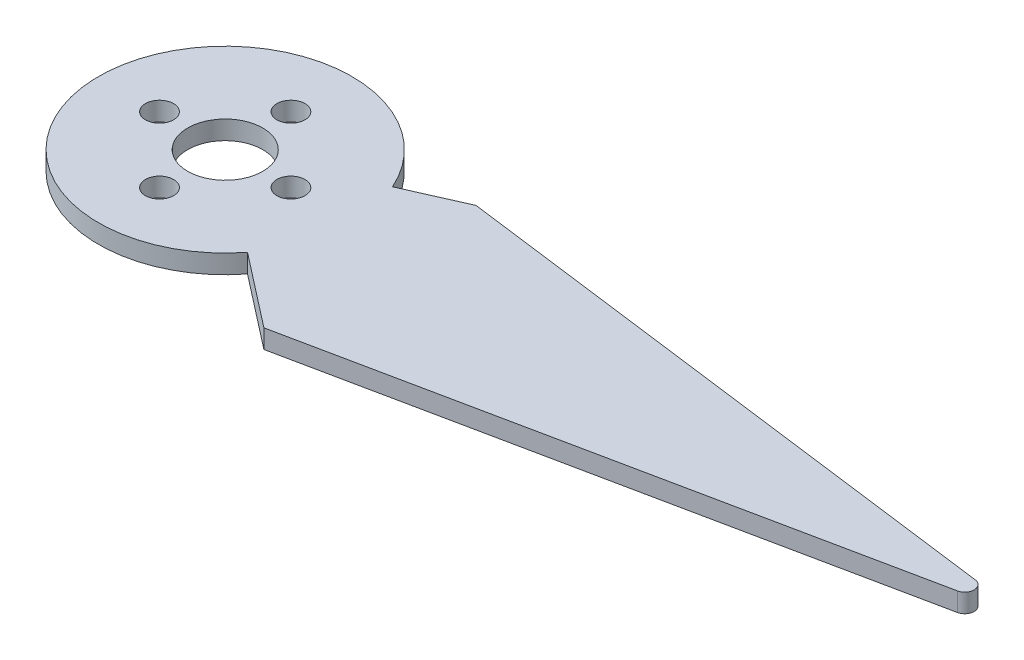
SolidWorks part; units mm, degrees
ref_plane "Alzado" through (0, 0, 0) normal (0, 0, 1) x (1, 0, 0)
ref_plane "Planta" through (0, 0, 0) normal (0, 1, 0) x (1, 0, 0)
ref_plane "Vista lateral" through (0, 0, 0) normal (1, 0, 0) x (0, 0, -1)
sketch "Croquis7" plane through (0, 0, 0) normal (0, 1, 0) x (1, 0, 0)
  line L0 (10.6592, -8.2848) -> (18.5, -14.3789)
  line L1 (18.5, -14.3789) -> (79.7101, -1.7047)
  line L2 (79.6363, 0.2662) -> (18.5, 8.2157)
  line L3 (18.5, 8.2157) -> (12.3377, 5.4806)
  line L4 (18.5, 8.2157) -> (18.5, -14.3789) construction
  arc A0 (10.6592, -8.2848) -> (12.3377, 5.4806) centre (0, 0) cw
  arc A1 (79.7101, -1.7047) -> (79.6363, 0.2662) centre (79.5074, -0.7255) ccw
  point P8 (85.5284, -0.5)
  dimension "D1" = 13.5002
  dimension "D2" = 1
  dimension "D4" = 12.3377
  dimension "D5" = 18.5
  dimension "D6" = 85.5284
  dimension "D7" = 8.2157
  dimension "D8" = 0.5
  dimension "D9" = 8.2848
base flange "Brida base1" sketch "Croquis7" thickness 2 reverse thickness direction no parameters "D1"=1
sketch "Croquis12" plane through (0, 0, 0) normal (0, 1, 0) x (1, 0, 0)
  circle A0 centre (0, 0) radius 4
  dimension "D1" = 8
extrude "Cortar-Extruir1" cut sketch "Croquis12" against normal blind 2 normal cut yes
sketch "Croquis13" plane through (0, 0, 0) normal (0, 1, 0) x (1, 0, 0)
  circle A0 centre (0, 7) radius 1.5
extrude "Cortar-Extruir2" cut sketch "Croquis13" against normal blind 2 normal cut yes
pattern_circular "MatrizC1" count 4 every 90 about axis through (0, 0, 0) along (0, 1, 0) of "Cortar-Extruir2"
sketch "Líneas de pliegue1" plane through (0, 0, 0) normal (0, 1, 0) x (1, 0, 0)
sketch "Cuadro delimitador1" plane through (0, 0, 0) normal (0, 1, 0) x (1, 0, 0)
sheet metal parameters "Chapa metálica1" thickness 2 parameters "D1"=1
flat pattern "Chapa desplegada1" [suppressed]
sketch "Líneas de pliegue2" plane through (0, 0, 0) normal (0, 1, 0) x (1, 0, 0)
sketch "Cuadro delimitador2" [suppressed] plane through (0, 0, 0) normal (0, 1, 0) x (1, 0, 0)
sheet metal parameters "Chapa metálica2" thickness 2 parameters "D1"=1
flat pattern "Chapa desplegada1"
sketch "Líneas de pliegue2" plane through (0, 0, 0) normal (0, 1, 0) x (1, 0, 0)
sketch "Cuadro delimitador2" [suppressed] plane through (0, 0, 0) normal (0, 1, 0) x (1, 0, 0)
sheet metal parameters "Chapa metálica3" thickness 2 parameters "D1"=1
flat pattern "Chapa desplegada1"
sketch "Líneas de pliegue2" plane through (0, 0, 0) normal (0, 1, 0) x (1, 0, 0)
sketch "Cuadro delimitador2" [suppressed] plane through (0, 0, 0) normal (0, 1, 0) x (1, 0, 0)
sheet metal parameters "Chapa metálica4" thickness 2 parameters "D1"=1
flat pattern "Chapa desplegada1"
sketch "Líneas de pliegue2" plane through (0, 0, 0) normal (0, 1, 0) x (1, 0, 0)
sketch "Cuadro delimitador2" [suppressed] plane through (0, 0, 0) normal (0, 1, 0) x (1, 0, 0)
